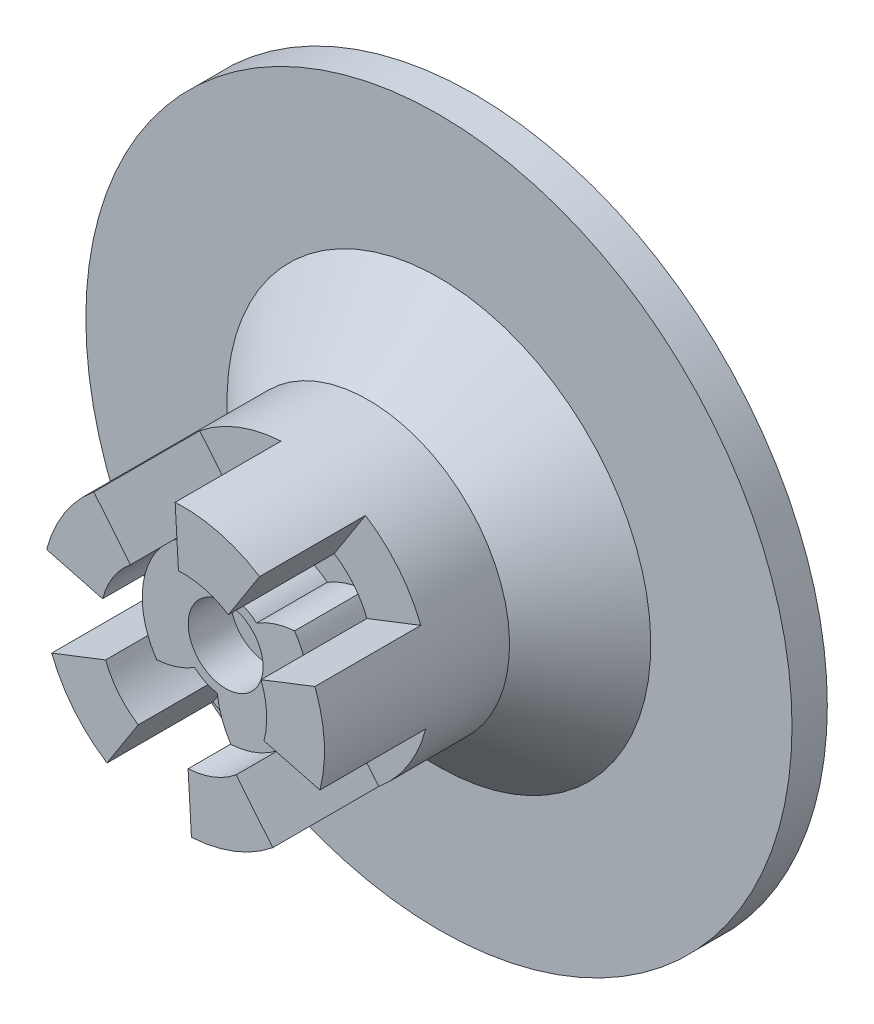
SolidWorks part; units mm, degrees
note: The reader was unsure of these and kept them because the rebuilt part matched: shared geometry of "Sketch11<5>", "Sketch11<6>".
ref_plane "Front Plane" through (0, 0, 0) normal (0, 0, 1) x (1, 0, 0)
ref_plane "Top Plane" through (0, 0, 0) normal (0, 1, 0) x (1, 0, 0)
ref_plane "Right Plane" through (0, 0, 0) normal (1, 0, 0) x (0, 0, -1)
sketch "Sketch2" plane through (0, 0, 0) normal (1, 0, 0) x (0, 0, -1)
  line L0 (-13.081, 0) -> (-13.081, 9.525)
  line L1 (-13.081, -31.75) -> (13.081, -31.75) construction
  line L2 (-13.081, -31.75) -> (-13.081, 9.525) construction
  line L3 (-9.906, 31.75) -> (13.081, 31.75) construction
  line L4 (13.081, -31.75) -> (13.081, 31.75) construction
  line L5 (-13.081, -31.75) -> (13.081, 31.75) construction
  line L6 (-13.081, 31.75) -> (-9.906, 24.0437) construction
  line L7 (-13.081, 31.75) -> (-9.906, 31.75) construction
  line L8 (-9.906, 31.75) -> (-9.906, 24.0437) construction
  line L9 (-9.906, 12.7) -> (9.906, 12.7)
  line L10 (9.906, 12.7) -> (9.906, 31.75)
  line L11 (9.906, 31.75) -> (13.081, 31.75)
  line L12 (13.081, 31.75) -> (13.081, 0)
  line L13 (13.081, 0) -> (-13.081, 0)
  line L14 (-13.081, -31.75) -> (-13.081, 0) construction
  line L15 (-9.906, 12.7) -> (-13.081, 12.7)
  line L16 (-9.906, 24.0437) -> (-5.2324, 12.7) construction
  line L17 (-5.2324, 12.7) -> (13.081, -31.75) construction
  line L18 (-9.906, 24.0437) -> (-9.906, 12.7) construction
  line L19 (-13.081, 12.7) -> (-13.081, 31.75) construction
  line L20 (-13.081, 12.7) -> (-13.081, 31.75) construction
  line L21 (-13.081, 31.75) -> (-9.906, 31.75) construction
  line L22 (-9.906, 12.7) -> (-9.906, 9.525) construction
  line L23 (-9.906, 9.525) -> (-13.081, 9.525) construction
  line L24 (-13.081, 9.525) -> (-13.081, 12.7)
  line L25 (-13.081, 9.525) -> (-13.081, 12.7) construction
  point P0 (0, 0)
  dimension "D1" = 63.5
  dimension "D2" = 26.162
  dimension "D3" = 3.175
  dimension "D4" = 12.7
  dimension "D5" = 3.175
  dimension "D6" = 9.525
revolve "Revolve1" add sketch "Sketch2" angle 360 about L13
sketch "Sketch11" plane through (0, 0, 13.081) normal (0, 0, 1) x (1, 0, 0)
  circle A0 centre (0, 0) radius 3.3672 construction
  arc A1 (6.1956, 4.2266) -> (2.7802, 3.1214) centre (6.7426, -3.2935) ccw construction
  arc A2 (2.7802, 3.1214) -> (0.749, 4.1123) centre (0, 0) ccw construction
  arc A3 (-0.749, -4.1123) -> (0.482, -7.4845) centre (6.7457, -3.2871) ccw construction
  arc A4 (-2.7802, -3.1214) -> (-0.749, -4.1123) centre (0, 0) ccw construction
  arc A5 (0.749, 4.1123) -> (-0.482, 7.4845) centre (-6.7457, 3.2871) ccw construction
  arc A6 (-6.1956, -4.2266) -> (-2.7802, -3.1214) centre (-6.7426, 3.2935) ccw construction
  circle A7 centre (0, 0) radius 7.5 construction
  circle A8 centre (0, 0) radius 3.3672
  arc A9 (6.1956, 4.2266) -> (2.7802, 3.1214) centre (6.7426, -3.2935) ccw
  arc A10 (2.7802, 3.1214) -> (0.749, 4.1123) centre (0, 0) ccw
  arc A11 (-0.749, -4.1123) -> (0.482, -7.4845) centre (6.7457, -3.2871) ccw
  arc A12 (-2.7802, -3.1214) -> (-0.749, -4.1123) centre (0, 0) ccw
  arc A13 (0.749, 4.1123) -> (-0.482, 7.4845) centre (-6.7457, 3.2871) ccw
  arc A14 (-6.1956, -4.2266) -> (-2.7802, -3.1214) centre (-6.7426, 3.2935) ccw
  circle A15 centre (0, 0) radius 7.5
extrude "Cut-Extrude5" cut sketch "Sketch11" against normal blind 3.81 contours A14 A15 A11 A12 | A13 A15 A14 A12 A11 A9 A10 A8 | A8 | A9 A15 A13 A10
extrude "Cut-Extrude7" cut sketch "Sketch11<5>" against normal blind 7.62 contours A8
sketch "Sketch11<5>" plane through (0, 0, 13.081) normal (0, 0, 1) x (1, 0, 0) same geometry as "Sketch11"
extrude "Cut-Extrude8" cut sketch "Sketch11<6>" against normal blind 10.16 contours A14 A15 A11 A12 | A9 A15 A13 A10
sketch "Sketch11<6>" plane through (0, 0, 13.081) normal (0, 0, 1) x (1, 0, 0) same geometry as "Sketch11"
sketch "Sketch13" plane through (0, 0, -13.081) normal (0, 0, -1) x (-1, 0, 0)
  circle A0 centre (0, 0) radius 6.35
extrude "Cut-Extrude10" cut sketch "Sketch13" against normal blind 12.192
chamfer "Chamfer1" distance 3.81 angle 45 1 edges at (-6.35, 0, -0.889)
chamfer "Chamfer2" distance 6.35 angle 45 1 edges at (0, 12.7, -9.906)
sketch "Sketch14" plane through (0, 0, 13.081) normal (0, 0, 1) x (1, 0, 0)
  line L0 (11.832, 4.6146) -> (6.9874, 2.7251) construction
  line L1 (12.2846, -3.2214) -> (7.2547, -1.9024) construction
  line L2 (-12.2846, 3.2214) -> (-7.2547, 1.9024)
  line L3 (-4.751, 5.8033) -> (-8.045, 9.8269)
  line L4 (-12.2846, 3.2214) -> (-7.2547, 1.9024)
  line L5 (-4.751, 5.8033) -> (-8.045, 9.8269)
  line L6 (-6.8599, -10.6879) -> (-4.0511, -6.3118)
  line L7 (-6.9874, -2.7251) -> (-11.832, -4.6146)
  line L8 (-6.8599, -10.6879) -> (-4.0511, -6.3118)
  line L9 (-6.9874, -2.7251) -> (-11.832, -4.6146)
  line L10 (0.4325, -7.4875) -> (0.7324, -12.6789)
  line L11 (8.045, -9.8269) -> (4.751, -5.8033)
  line L12 (0.4325, -7.4875) -> (0.7324, -12.6789)
  line L13 (8.045, -9.8269) -> (4.751, -5.8033)
  line L14 (4.0511, 6.3118) -> (6.8599, 10.6879)
  line L15 (-0.7324, 12.6789) -> (-0.4325, 7.4875)
  line L16 (4.0511, 6.3118) -> (6.8599, 10.6879)
  line L17 (-0.7324, 12.6789) -> (-0.4325, 7.4875)
  line L18 (11.832, 4.6146) -> (6.9874, 2.7251)
  line L19 (12.2846, -3.2214) -> (7.2547, -1.9024)
  arc A0 (0.4325, -7.4875) -> (4.751, -5.8033) centre (0, 0) ccw construction
  circle A1 centre (0, 0) radius 7.5
  circle A2 centre (0, 0) radius 7.5
  arc A3 (12.2846, -3.2214) -> (11.832, 4.6146) centre (0, 0) ccw construction
  arc A4 (-4.751, 5.8033) -> (-7.2547, 1.9024) centre (0, 0) ccw
  arc A5 (-8.045, 9.8269) -> (-12.2846, 3.2214) centre (0, 0) ccw
  arc A6 (-4.751, 5.8033) -> (-7.2547, 1.9024) centre (0, 0) ccw
  arc A7 (-8.045, 9.8269) -> (-12.2846, 3.2214) centre (0, 0) ccw
  arc A8 (-6.9874, -2.7251) -> (-4.0511, -6.3118) centre (0, 0) ccw
  arc A9 (-11.832, -4.6146) -> (-6.8599, -10.6879) centre (0, 0) ccw
  arc A10 (-6.9874, -2.7251) -> (-4.0511, -6.3118) centre (0, 0) ccw
  arc A11 (-11.832, -4.6146) -> (-6.8599, -10.6879) centre (0, 0) ccw
  arc A12 (0.4325, -7.4875) -> (4.751, -5.8033) centre (0, 0) ccw
  arc A13 (0.7324, -12.6789) -> (8.045, -9.8269) centre (0, 0) ccw
  arc A14 (0.4325, -7.4875) -> (4.751, -5.8033) centre (0, 0) ccw
  arc A15 (0.7324, -12.6789) -> (8.045, -9.8269) centre (0, 0) ccw
  arc A16 (4.0511, 6.3118) -> (-0.4325, 7.4875) centre (0, 0) ccw
  arc A17 (6.8599, 10.6879) -> (-0.7324, 12.6789) centre (0, 0) ccw
  arc A18 (4.0511, 6.3118) -> (-0.4325, 7.4875) centre (0, 0) ccw
  arc A19 (6.8599, 10.6879) -> (-0.7324, 12.6789) centre (0, 0) ccw
  arc A20 (-4.751, 5.8033) -> (-7.2547, 1.9024) centre (0, 0) ccw construction
  arc A21 (-6.9874, -2.7251) -> (-4.0511, -6.3118) centre (0, 0) ccw construction
  arc A22 (4.0511, 6.3118) -> (-0.4325, 7.4875) centre (0, 0) ccw construction
  arc A23 (0.4325, -7.4875) -> (4.751, -5.8033) centre (0, 0) ccw
  arc A24 (12.2846, -3.2214) -> (11.832, 4.6146) centre (0, 0) ccw
  arc A25 (-4.751, 5.8033) -> (-7.2547, 1.9024) centre (0, 0) ccw
  arc A26 (-6.9874, -2.7251) -> (-4.0511, -6.3118) centre (0, 0) ccw
  arc A27 (4.0511, 6.3118) -> (-0.4325, 7.4875) centre (0, 0) ccw
  dimension "D1" = 0
  dimension "D2" = 0
  dimension "D3" = 0
  dimension "D4" = 0
  dimension "D5" = 0
extrude "Cut-Extrude11" cut sketch "Sketch14" against normal blind 9.525
